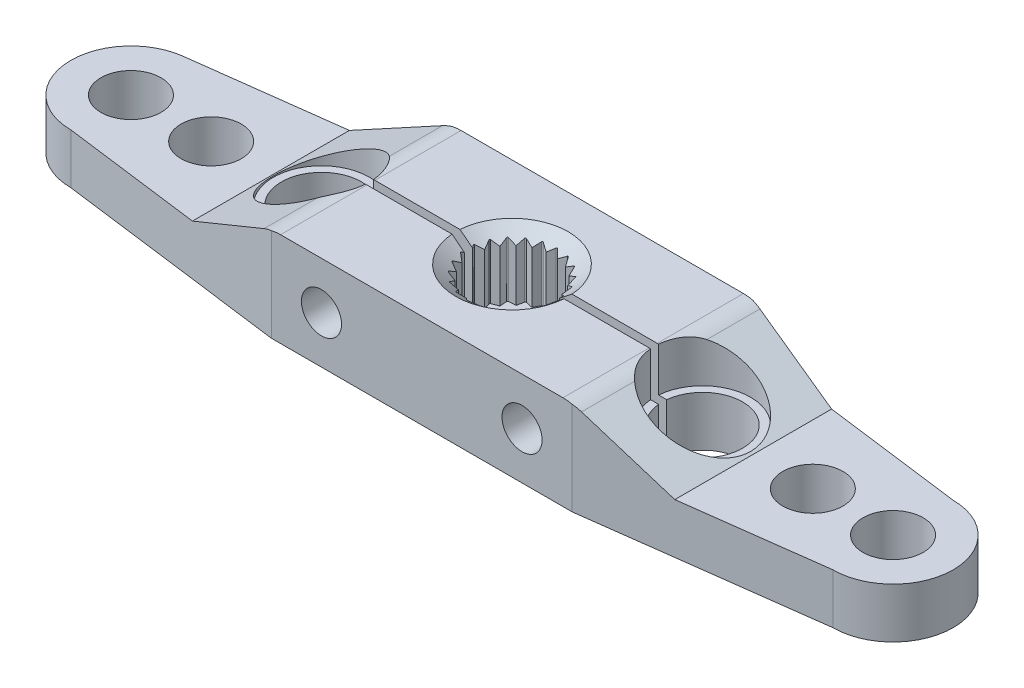
SolidWorks part; units mm, degrees
material "6061 Alloy"
ref_plane "Front Plane" through (0, 0, 0) normal (0, 0, 1) x (1, 0, 0)
ref_plane "Top Plane" through (0, 0, 0) normal (0, 1, 0) x (1, 0, 0)
ref_plane "Right Plane" through (0, 0, 0) normal (1, 0, 0) x (0, 0, -1)
sketch "Sketch1" plane through (0, 0, 0) normal (0, 1, 0) x (1, 0, 0)
  line L0 (-0.3401, -2.1423) -> (-0.1004, -1.9025) construction
  line L1 (-0.1004, -1.9025) -> (0.1972, -2.065) construction
  line L2 (0.2621, -2.046) -> (0.4246, -1.7484) construction
  line L3 (0.4246, -1.7484) -> (0.7558, -1.8205) construction
  line L4 (0.8127, -1.7839) -> (0.8848, -1.4526) construction
  line L5 (0.8848, -1.4526) -> (1.223, -1.4284) construction
  line L6 (1.2673, -1.3773) -> (1.2431, -1.0392) construction
  line L7 (1.2431, -1.0392) -> (1.5607, -0.9207) construction
  line L8 (1.5888, -0.8592) -> (1.4703, -0.5415) construction
  line L9 (1.4703, -0.5415) -> (1.7417, -0.3384) construction
  line L10 (1.7514, -0.2714) -> (1.5482, 0) construction
  line L11 (1.5482, 0) -> (1.7514, 0.2714) construction
  line L12 (1.7417, 0.3384) -> (1.4703, 0.5415) construction
  line L13 (1.4703, 0.5415) -> (1.5888, 0.8592) construction
  line L14 (1.5607, 0.9207) -> (1.2431, 1.0392) construction
  line L15 (1.2431, 1.0392) -> (1.2673, 1.3773) construction
  line L16 (1.223, 1.4284) -> (0.8848, 1.4526) construction
  line L17 (0.8848, 1.4526) -> (0.8127, 1.7839) construction
  line L18 (0.7558, 1.8205) -> (0.4246, 1.7484) construction
  line L19 (0.4246, 1.7484) -> (0.2621, 2.046) construction
  line L20 (0.1972, 2.065) -> (-0.1004, 1.9025) construction
  line L21 (-0.1004, 1.9025) -> (-0.3401, 2.1423) construction
  line L22 (-0.4077, 2.1423) -> (-0.6475, 1.9025) construction
  line L23 (-0.6475, 1.9025) -> (-0.945, 2.065) construction
  line L24 (-1.0099, 2.046) -> (-1.1724, 1.7484) construction
  line L25 (-1.1724, 1.7484) -> (-1.5037, 1.8205) construction
  line L26 (-1.5606, 1.7839) -> (-1.6326, 1.4526) construction
  line L27 (-1.6326, 1.4526) -> (-1.9708, 1.4284) construction
  line L28 (-2.0151, 1.3773) -> (-1.9909, 1.0392) construction
  line L29 (-1.9909, 1.0392) -> (-2.3085, 0.9207) construction
  line L30 (-2.3366, 0.8592) -> (-2.2182, 0.5415) construction
  line L31 (-2.2182, 0.5415) -> (-2.4896, 0.3384) construction
  line L32 (-2.4992, 0.2714) -> (-2.296, 0) construction
  line L33 (-2.296, 0) -> (-2.4992, -0.2714) construction
  line L34 (-2.4896, -0.3384) -> (-2.2182, -0.5415) construction
  line L35 (-2.2182, -0.5415) -> (-2.3366, -0.8592) construction
  line L36 (-2.3085, -0.9207) -> (-1.9909, -1.0392) construction
  line L37 (-1.9909, -1.0392) -> (-2.0151, -1.3773) construction
  line L38 (-1.9708, -1.4284) -> (-1.6326, -1.4526) construction
  line L39 (-1.6326, -1.4526) -> (-1.5606, -1.7839) construction
  line L40 (-1.5037, -1.8205) -> (-1.1724, -1.7484) construction
  line L41 (-1.1724, -1.7484) -> (-1.0099, -2.046) construction
  line L42 (-0.945, -2.065) -> (-0.6475, -1.9025) construction
  line L43 (-0.6475, -1.9025) -> (-0.4077, -2.1423) construction
  line L44 (-15.3739, 0) -> (14.6261, 0) construction
  line L46 (14.6261, 0) -> (18.6261, 0) construction
  line L47 (-0.3739, 0) -> (-0.3739, 4.5) construction
  line L48 (21.6261, 0) -> (21.6261, 4.5) construction
  line L49 (-7.8739, 4.5) -> (7.1261, 4.5)
  line L50 (18.6261, 0) -> (21.6261, 0) construction
  line L51 (7.1261, 4.5) -> (18.6261, 3)
  line L52 (7.1261, 4.5) -> (7.1261, -4.5) construction
  line L53 (7.1261, -4.5) -> (-7.8739, -4.5)
  line L54 (7.1261, -4.5) -> (18.6261, -3)
  line L55 (-7.8739, -4.5) -> (-19.3739, -3)
  line L56 (-7.8739, 4.5) -> (-7.8739, -4.5) construction
  line L57 (-19.3739, 0) -> (-22.3739, 0) construction
  line L59 (-15.3739, 0) -> (-19.3739, 0) construction
  line L61 (-7.8739, 4.5) -> (-19.7557, 2.9756)
  circle A0 centre (-0.3739, 0) radius 4.5 construction
  arc A1 (-0.4077, -2.1423) -> (-0.3401, -2.1423) centre (-0.3739, -2.1085) ccw construction
  arc A2 (0.1972, -2.065) -> (0.2621, -2.046) centre (0.2201, -2.023) ccw construction
  arc A3 (0.7558, -1.8205) -> (0.8127, -1.7839) centre (0.766, -1.7737) ccw construction
  arc A4 (1.223, -1.4284) -> (1.2673, -1.3773) centre (1.2195, -1.3807) ccw construction
  arc A5 (1.5607, -0.9207) -> (1.5888, -0.8592) centre (1.544, -0.8759) ccw construction
  arc A6 (1.7417, -0.3384) -> (1.7514, -0.2714) centre (1.7131, -0.3001) ccw construction
  arc A7 (1.7514, 0.2714) -> (1.7417, 0.3384) centre (1.7131, 0.3001) ccw construction
  arc A8 (1.5888, 0.8592) -> (1.5607, 0.9207) centre (1.544, 0.8759) ccw construction
  arc A9 (1.2673, 1.3773) -> (1.223, 1.4284) centre (1.2195, 1.3807) ccw construction
  arc A10 (0.8127, 1.7839) -> (0.7558, 1.8205) centre (0.766, 1.7737) ccw construction
  arc A11 (0.2621, 2.046) -> (0.1972, 2.065) centre (0.2201, 2.023) ccw construction
  arc A12 (-0.3401, 2.1423) -> (-0.4077, 2.1423) centre (-0.3739, 2.1085) ccw construction
  arc A13 (-0.945, 2.065) -> (-1.0099, 2.046) centre (-0.9679, 2.023) ccw construction
  arc A14 (-1.5037, 1.8205) -> (-1.5606, 1.7839) centre (-1.5138, 1.7737) ccw construction
  arc A15 (-1.9708, 1.4284) -> (-2.0151, 1.3773) centre (-1.9674, 1.3807) ccw construction
  arc A16 (-2.3085, 0.9207) -> (-2.3366, 0.8592) centre (-2.2918, 0.8759) ccw construction
  arc A17 (-2.4896, 0.3384) -> (-2.4992, 0.2714) centre (-2.4609, 0.3001) ccw construction
  arc A18 (-2.4992, -0.2714) -> (-2.4896, -0.3384) centre (-2.4609, -0.3001) ccw construction
  arc A19 (-2.3366, -0.8592) -> (-2.3085, -0.9207) centre (-2.2918, -0.8759) ccw construction
  arc A20 (-2.0151, -1.3773) -> (-1.9708, -1.4284) centre (-1.9674, -1.3807) ccw construction
  arc A21 (-1.5606, -1.7839) -> (-1.5037, -1.8205) centre (-1.5138, -1.7737) ccw construction
  arc A22 (-1.0099, -2.046) -> (-0.945, -2.065) centre (-0.9679, -2.023) ccw construction
  circle A23 centre (18.6261, 0) radius 1.5
  circle A24 centre (14.6261, 0) radius 1.5
  arc A25 (18.6261, -3) -> (18.6261, 3) centre (18.6261, 0) ccw
  circle A26 centre (9.1261, 0) radius 2
  circle A27 centre (-9.8739, 0) radius 2
  arc A28 (-19.3739, -3) -> (-19.7557, 2.9756) centre (-19.3739, 0) cw
  circle A29 centre (-15.3739, 0) radius 1.5
  circle A30 centre (-19.3739, 0) radius 1.5
  circle A31 centre (-0.3739, 0) radius 1.5
  circle A32 centre (-0.3739, 0) radius 2.1425 construction
  point P109 (-0.3739, -4.5)
  dimension "D2" = 3
  dimension "D3" = 3
  dimension "D4" = 4
  dimension "D5" = 4
  dimension "D6" = 3
  dimension "D7" = 3
  dimension "D8" = 3
  dimension "D9" = 3
  dimension "D12" = 30
  dimension "D1" = 22
  dimension "D10" = 44
  dimension "D11" = 15
extrude "Boss-Extrude1" add sketch "Sketch1" along normal blind 2.5
sketch "Sketch3" plane through (0, 2.5, 0) normal (0, 1, 0) x (1, 0, 0)
  line L0 (-0.3386, -2.2396) -> (-0.0879, -1.989)
  line L1 (-0.0879, -1.989) -> (0.2231, -2.1589)
  line L2 (0.291, -2.139) -> (0.4609, -1.8279)
  line L3 (0.4609, -1.8279) -> (0.8072, -1.9032)
  line L4 (0.8667, -1.865) -> (0.942, -1.5187)
  line L5 (0.942, -1.5187) -> (1.2955, -1.4934)
  line L6 (1.3419, -1.4399) -> (1.3166, -1.0864)
  line L7 (1.3166, -1.0864) -> (1.6487, -0.9625)
  line L8 (1.678, -0.8982) -> (1.5542, -0.5661)
  line L9 (1.5542, -0.5661) -> (1.8379, -0.3537)
  line L10 (1.848, -0.2837) -> (1.6356, 0)
  line L11 (1.6356, 0) -> (1.848, 0.2837)
  line L12 (1.8379, 0.3537) -> (1.5542, 0.5661)
  line L13 (1.5542, 0.5661) -> (1.678, 0.8982)
  line L14 (1.6487, 0.9625) -> (1.3166, 1.0864)
  line L15 (1.3166, 1.0864) -> (1.3419, 1.4399)
  line L16 (1.2955, 1.4934) -> (0.942, 1.5187)
  line L17 (0.942, 1.5187) -> (0.8667, 1.865)
  line L18 (0.8072, 1.9032) -> (0.4609, 1.8279)
  line L19 (0.4609, 1.8279) -> (0.291, 2.139)
  line L20 (0.2231, 2.1589) -> (-0.0879, 1.989)
  line L21 (-0.0879, 1.989) -> (-0.3386, 2.2396)
  line L22 (-0.4093, 2.2396) -> (-0.6599, 1.989)
  line L23 (-0.6599, 1.989) -> (-0.971, 2.1589)
  line L24 (-1.0388, 2.139) -> (-1.2087, 1.8279)
  line L25 (-1.2087, 1.8279) -> (-1.555, 1.9032)
  line L26 (-1.6145, 1.865) -> (-1.6898, 1.5187)
  line L27 (-1.6898, 1.5187) -> (-2.0434, 1.4934)
  line L28 (-2.0897, 1.4399) -> (-2.0644, 1.0864)
  line L29 (-2.0644, 1.0864) -> (-2.3965, 0.9625)
  line L30 (-2.4259, 0.8982) -> (-2.302, 0.5661)
  line L31 (-2.302, 0.5661) -> (-2.5857, 0.3537)
  line L32 (-2.5958, 0.2837) -> (-2.3834, 0)
  line L33 (-2.3834, 0) -> (-2.5958, -0.2837)
  line L34 (-2.5857, -0.3537) -> (-2.302, -0.5661)
  line L35 (-2.302, -0.5661) -> (-2.4259, -0.8982)
  line L36 (-2.3965, -0.9625) -> (-2.0644, -1.0864)
  line L37 (-2.0644, -1.0864) -> (-2.0897, -1.4399)
  line L38 (-2.0434, -1.4934) -> (-1.6898, -1.5187)
  line L39 (-1.6898, -1.5187) -> (-1.6145, -1.865)
  line L40 (-1.555, -1.9032) -> (-1.2087, -1.8279)
  line L41 (-1.2087, -1.8279) -> (-1.0388, -2.139)
  line L42 (-0.971, -2.1589) -> (-0.6599, -1.989)
  line L43 (-0.6599, -1.989) -> (-0.4093, -2.2396)
  line L44 (-7.8739, -4.5) -> (-7.8739, 4.5)
  line L45 (-7.8739, 4.5) -> (7.1261, 4.5)
  line L46 (7.1261, 4.5) -> (7.1261, -4.5)
  line L47 (7.1261, -4.5) -> (-7.8739, -4.5)
  circle A0 centre (-0.3739, 0) radius 2.2399 construction
  arc A1 (-0.4093, -2.2396) -> (-0.3386, -2.2396) centre (-0.3739, -2.2043) ccw
  arc A2 (0.2231, -2.1589) -> (0.291, -2.139) centre (0.2471, -2.115) ccw
  arc A3 (0.8072, -1.9032) -> (0.8667, -1.865) centre (0.8178, -1.8544) ccw
  arc A4 (1.2955, -1.4934) -> (1.3419, -1.4399) centre (1.292, -1.4435) ccw
  arc A5 (1.6487, -0.9625) -> (1.678, -0.8982) centre (1.6312, -0.9157) ccw
  arc A6 (1.8379, -0.3537) -> (1.848, -0.2837) centre (1.8079, -0.3137) ccw
  arc A7 (1.848, 0.2837) -> (1.8379, 0.3537) centre (1.8079, 0.3137) ccw
  arc A8 (1.678, 0.8982) -> (1.6487, 0.9625) centre (1.6312, 0.9157) ccw
  arc A9 (1.3419, 1.4399) -> (1.2955, 1.4934) centre (1.292, 1.4435) ccw
  arc A10 (0.8667, 1.865) -> (0.8072, 1.9032) centre (0.8178, 1.8544) ccw
  arc A11 (0.291, 2.139) -> (0.2231, 2.1589) centre (0.2471, 2.115) ccw
  arc A12 (-0.3386, 2.2396) -> (-0.4093, 2.2396) centre (-0.3739, 2.2043) ccw
  arc A13 (-0.971, 2.1589) -> (-1.0388, 2.139) centre (-0.9949, 2.115) ccw
  arc A14 (-1.555, 1.9032) -> (-1.6145, 1.865) centre (-1.5656, 1.8544) ccw
  arc A15 (-2.0434, 1.4934) -> (-2.0897, 1.4399) centre (-2.0398, 1.4435) ccw
  arc A16 (-2.3965, 0.9625) -> (-2.4259, 0.8982) centre (-2.379, 0.9157) ccw
  arc A17 (-2.5857, 0.3537) -> (-2.5958, 0.2837) centre (-2.5558, 0.3137) ccw
  arc A18 (-2.5958, -0.2837) -> (-2.5857, -0.3537) centre (-2.5558, -0.3137) ccw
  arc A19 (-2.4259, -0.8982) -> (-2.3965, -0.9625) centre (-2.379, -0.9157) ccw
  arc A20 (-2.0897, -1.4399) -> (-2.0434, -1.4934) centre (-2.0398, -1.4435) ccw
  arc A21 (-1.6145, -1.865) -> (-1.555, -1.9032) centre (-1.5656, -1.8544) ccw
  arc A22 (-1.0388, -2.139) -> (-0.971, -2.1589) centre (-0.9949, -2.115) ccw
extrude "Boss-Extrude2" add sketch "Sketch3" along normal blind 2.2
ref_plane "Plane1" through (-7.8739, 2.5, 0) normal (0, 0, 1) x (1, 0, 0)
ref_plane "Plane2" through (-7.8739, 4.7, -4.5) normal (0, 0, 1) x (1, 0, 0)
sketch "Sketch7" plane through (-0.7089, 0, 5.4346) normal (-0.1293, 0, 0.9916) x (0.9916, 0, 0.1293)
  line L0 (-7.2257, 2.5) -> (-7.2257, 4.7)
  line L1 (-7.2257, 4.7) -> (-11.791, 2.5)
  line L2 (-18.8232, 2.5) -> (-7.2257, 2.5) construction
  line L3 (-11.791, 2.5) -> (-7.2257, 2.5)
extrude "Boss-Extrude3" add sketch "Sketch7" along direction (0, 0, 1) on the side against the normal up to surface (9 mm away) up to face at (-13.8148, 1.25, -3.7378)
sketch "Sketch8" plane through (0, 2.5, 0) normal (0, -1, 0) x (1, 0, 0)
  circle A0 centre (-9.8739, 0) radius 2.4
  circle A1 centre (-9.8739, 0) radius 2
  circle A2 centre (-9.8739, 0) radius 2
  dimension "D1" = 0
extrude "Cut-Extrude1" cut sketch "Sketch8" against normal through all contours A0
sketch "Sketch9" plane through (0.6963, 0, -5.3387) normal (0.1293, 0, -0.9916) x (-0.9916, 0, -0.1293)
  line L0 (-6.4842, 2.5) -> (-6.4842, 4.7)
  line L1 (-6.4842, 4.7) -> (-11.0494, 2.5)
  line L2 (-18.0816, 2.5) -> (-6.4842, 2.5) construction
  line L3 (-11.0494, 2.5) -> (-6.4842, 2.5)
extrude "Boss-Extrude4" add sketch "Sketch9" along direction (0, 0, -1) on the side against the normal up to surface (9 mm away) up to face at (12.8761, 1.25, 3.75)
sketch "Sketch10" plane through (0, 2.5, 0) normal (0, -1, 0) x (1, 0, 0)
  circle A0 centre (9.1261, 0) radius 2.4
  circle A1 centre (9.1261, 0) radius 2
  circle A2 centre (9.1261, 0) radius 2
  dimension "D1" = 0
extrude "Cut-Extrude2" cut sketch "Sketch10" against normal blind 2.5 contours A0
sketch "Sketch18" plane through (0, 2.5, 0) normal (0, 1, 0) x (1, 0, 0)
  line L44 (-0.3386, -2.2396) -> (-0.0879, -1.989)
  line L45 (-0.0879, -1.989) -> (0.2231, -2.1589)
  line L46 (0.291, -2.139) -> (0.4609, -1.8279)
  line L47 (0.4609, -1.8279) -> (0.8072, -1.9032)
  line L48 (0.8667, -1.865) -> (0.942, -1.5187)
  line L49 (0.942, -1.5187) -> (1.2955, -1.4934)
  line L50 (1.3419, -1.4399) -> (1.3166, -1.0864)
  line L51 (1.3166, -1.0864) -> (1.6487, -0.9625)
  line L52 (1.678, -0.8982) -> (1.5542, -0.5661)
  line L53 (1.5542, -0.5661) -> (1.8379, -0.3537)
  line L54 (1.848, -0.2837) -> (1.6356, 0)
  line L55 (1.6356, 0) -> (1.848, 0.2837)
  line L56 (1.8379, 0.3537) -> (1.5542, 0.5661)
  line L57 (1.5542, 0.5661) -> (1.678, 0.8982)
  line L58 (1.6487, 0.9625) -> (1.3166, 1.0864)
  line L59 (1.3166, 1.0864) -> (1.3419, 1.4399)
  line L60 (1.2955, 1.4934) -> (0.942, 1.5187)
  line L61 (0.942, 1.5187) -> (0.8667, 1.865)
  line L62 (0.8072, 1.9032) -> (0.4609, 1.8279)
  line L63 (0.4609, 1.8279) -> (0.291, 2.139)
  line L64 (0.2231, 2.1589) -> (-0.0879, 1.989)
  line L65 (-0.0879, 1.989) -> (-0.3386, 2.2396)
  line L66 (-0.4093, 2.2396) -> (-0.6599, 1.989)
  line L67 (-0.6599, 1.989) -> (-0.971, 2.1589)
  line L68 (-1.0388, 2.139) -> (-1.2087, 1.8279)
  line L69 (-1.2087, 1.8279) -> (-1.555, 1.9032)
  line L70 (-1.6145, 1.865) -> (-1.6898, 1.5187)
  line L71 (-1.6898, 1.5187) -> (-2.0434, 1.4934)
  line L72 (-2.0897, 1.4399) -> (-2.0644, 1.0864)
  line L73 (-2.0644, 1.0864) -> (-2.3965, 0.9625)
  line L74 (-2.4259, 0.8982) -> (-2.302, 0.5661)
  line L75 (-2.302, 0.5661) -> (-2.5857, 0.3537)
  line L76 (-2.5958, 0.2837) -> (-2.3834, 0)
  line L77 (-2.3834, 0) -> (-2.5958, -0.2837)
  line L78 (-2.5857, -0.3537) -> (-2.302, -0.5661)
  line L79 (-2.302, -0.5661) -> (-2.4259, -0.8982)
  line L80 (-2.3965, -0.9625) -> (-2.0644, -1.0864)
  line L81 (-2.0644, -1.0864) -> (-2.0897, -1.4399)
  line L82 (-2.0434, -1.4934) -> (-1.6898, -1.5187)
  line L83 (-1.6898, -1.5187) -> (-1.6145, -1.865)
  line L84 (-1.555, -1.9032) -> (-1.2087, -1.8279)
  line L85 (-1.2087, -1.8279) -> (-1.0388, -2.139)
  line L86 (-0.971, -2.1589) -> (-0.6599, -1.989)
  line L87 (-0.6599, -1.989) -> (-0.4093, -2.2396)
  line L88 (-0.3386, -2.2396) -> (-0.0879, -1.989)
  line L89 (-0.0879, -1.989) -> (0.2231, -2.1589)
  line L90 (0.291, -2.139) -> (0.4609, -1.8279)
  line L91 (0.4609, -1.8279) -> (0.8072, -1.9032)
  line L92 (0.8667, -1.865) -> (0.942, -1.5187)
  line L93 (0.942, -1.5187) -> (1.2955, -1.4934)
  line L94 (1.3419, -1.4399) -> (1.3166, -1.0864)
  line L95 (1.3166, -1.0864) -> (1.6487, -0.9625)
  line L96 (1.678, -0.8982) -> (1.5542, -0.5661)
  line L97 (1.5542, -0.5661) -> (1.8379, -0.3537)
  line L98 (1.848, -0.2837) -> (1.6356, 0)
  line L99 (1.6356, 0) -> (1.848, 0.2837)
  line L100 (1.8379, 0.3537) -> (1.5542, 0.5661)
  line L101 (1.5542, 0.5661) -> (1.678, 0.8982)
  line L102 (1.6487, 0.9625) -> (1.3166, 1.0864)
  line L103 (1.3166, 1.0864) -> (1.3419, 1.4399)
  line L104 (1.2955, 1.4934) -> (0.942, 1.5187)
  line L105 (0.942, 1.5187) -> (0.8667, 1.865)
  line L106 (0.8072, 1.9032) -> (0.4609, 1.8279)
  line L107 (0.4609, 1.8279) -> (0.291, 2.139)
  line L108 (0.2231, 2.1589) -> (-0.0879, 1.989)
  line L109 (-0.0879, 1.989) -> (-0.3386, 2.2396)
  line L110 (-0.4093, 2.2396) -> (-0.6599, 1.989)
  line L111 (-0.6599, 1.989) -> (-0.971, 2.1589)
  line L112 (-1.0388, 2.139) -> (-1.2087, 1.8279)
  line L113 (-1.2087, 1.8279) -> (-1.555, 1.9032)
  line L114 (-1.6145, 1.865) -> (-1.6898, 1.5187)
  line L115 (-1.6898, 1.5187) -> (-2.0434, 1.4934)
  line L116 (-2.0897, 1.4399) -> (-2.0644, 1.0864)
  line L117 (-2.0644, 1.0864) -> (-2.3965, 0.9625)
  line L118 (-2.4259, 0.8982) -> (-2.302, 0.5661)
  line L119 (-2.302, 0.5661) -> (-2.5857, 0.3537)
  line L120 (-2.5958, 0.2837) -> (-2.3834, 0)
  line L121 (-2.3834, 0) -> (-2.5958, -0.2837)
  line L122 (-2.5857, -0.3537) -> (-2.302, -0.5661)
  line L123 (-2.302, -0.5661) -> (-2.4259, -0.8982)
  line L124 (-2.3965, -0.9625) -> (-2.0644, -1.0864)
  line L125 (-2.0644, -1.0864) -> (-2.0897, -1.4399)
  line L126 (-2.0434, -1.4934) -> (-1.6898, -1.5187)
  line L127 (-1.6898, -1.5187) -> (-1.6145, -1.865)
  line L128 (-1.555, -1.9032) -> (-1.2087, -1.8279)
  line L129 (-1.2087, -1.8279) -> (-1.0388, -2.139)
  line L130 (-0.971, -2.1589) -> (-0.6599, -1.989)
  line L131 (-0.6599, -1.989) -> (-0.4093, -2.2396)
  circle A0 centre (-0.3739, 0) radius 1.5 construction
  circle A1 centre (-0.3739, 0) radius 1.5
  arc A22 (-0.4093, -2.2396) -> (-0.3386, -2.2396) centre (-0.3739, -2.2043) ccw
  arc A23 (0.2231, -2.1589) -> (0.291, -2.139) centre (0.2471, -2.115) ccw
  arc A24 (0.8072, -1.9032) -> (0.8667, -1.865) centre (0.8178, -1.8544) ccw
  arc A25 (1.2955, -1.4934) -> (1.3419, -1.4399) centre (1.292, -1.4435) ccw
  arc A26 (1.6487, -0.9625) -> (1.678, -0.8982) centre (1.6312, -0.9157) ccw
  arc A27 (1.8379, -0.3537) -> (1.848, -0.2837) centre (1.8079, -0.3137) ccw
  arc A28 (1.848, 0.2837) -> (1.8379, 0.3537) centre (1.8079, 0.3137) ccw
  arc A29 (1.678, 0.8982) -> (1.6487, 0.9625) centre (1.6312, 0.9157) ccw
  arc A30 (1.3419, 1.4399) -> (1.2955, 1.4934) centre (1.292, 1.4435) ccw
  arc A31 (0.8667, 1.865) -> (0.8072, 1.9032) centre (0.8178, 1.8544) ccw
  arc A32 (0.291, 2.139) -> (0.2231, 2.1589) centre (0.2471, 2.115) ccw
  arc A33 (-0.3386, 2.2396) -> (-0.4093, 2.2396) centre (-0.3739, 2.2043) ccw
  arc A34 (-0.971, 2.1589) -> (-1.0388, 2.139) centre (-0.9949, 2.115) ccw
  arc A35 (-1.555, 1.9032) -> (-1.6145, 1.865) centre (-1.5656, 1.8544) ccw
  arc A36 (-2.0434, 1.4934) -> (-2.0897, 1.4399) centre (-2.0398, 1.4435) ccw
  arc A37 (-2.3965, 0.9625) -> (-2.4259, 0.8982) centre (-2.379, 0.9157) ccw
  arc A38 (-2.5857, 0.3537) -> (-2.5958, 0.2837) centre (-2.5558, 0.3137) ccw
  arc A39 (-2.5958, -0.2837) -> (-2.5857, -0.3537) centre (-2.5558, -0.3137) ccw
  arc A40 (-2.4259, -0.8982) -> (-2.3965, -0.9625) centre (-2.379, -0.9157) ccw
  arc A41 (-2.0897, -1.4399) -> (-2.0434, -1.4934) centre (-2.0398, -1.4435) ccw
  arc A42 (-1.6145, -1.865) -> (-1.555, -1.9032) centre (-1.5656, -1.8544) ccw
  arc A43 (-1.0388, -2.139) -> (-0.971, -2.1589) centre (-0.9949, -2.115) ccw
  arc A44 (-0.4093, -2.2396) -> (-0.3386, -2.2396) centre (-0.3739, -2.2043) ccw
  arc A45 (0.2231, -2.1589) -> (0.291, -2.139) centre (0.2471, -2.115) ccw
  arc A46 (0.8072, -1.9032) -> (0.8667, -1.865) centre (0.8178, -1.8544) ccw
  arc A47 (1.2955, -1.4934) -> (1.3419, -1.4399) centre (1.292, -1.4435) ccw
  arc A48 (1.6487, -0.9625) -> (1.678, -0.8982) centre (1.6312, -0.9157) ccw
  arc A49 (1.8379, -0.3537) -> (1.848, -0.2837) centre (1.8079, -0.3137) ccw
  arc A50 (1.848, 0.2837) -> (1.8379, 0.3537) centre (1.8079, 0.3137) ccw
  arc A51 (1.678, 0.8982) -> (1.6487, 0.9625) centre (1.6312, 0.9157) ccw
  arc A52 (1.3419, 1.4399) -> (1.2955, 1.4934) centre (1.292, 1.4435) ccw
  arc A53 (0.8667, 1.865) -> (0.8072, 1.9032) centre (0.8178, 1.8544) ccw
  arc A54 (0.291, 2.139) -> (0.2231, 2.1589) centre (0.2471, 2.115) ccw
  arc A55 (-0.3386, 2.2396) -> (-0.4093, 2.2396) centre (-0.3739, 2.2043) ccw
  arc A56 (-0.971, 2.1589) -> (-1.0388, 2.139) centre (-0.9949, 2.115) ccw
  arc A57 (-1.555, 1.9032) -> (-1.6145, 1.865) centre (-1.5656, 1.8544) ccw
  arc A58 (-2.0434, 1.4934) -> (-2.0897, 1.4399) centre (-2.0398, 1.4435) ccw
  arc A59 (-2.3965, 0.9625) -> (-2.4259, 0.8982) centre (-2.379, 0.9157) ccw
  arc A60 (-2.5857, 0.3537) -> (-2.5958, 0.2837) centre (-2.5558, 0.3137) ccw
  arc A61 (-2.5958, -0.2837) -> (-2.5857, -0.3537) centre (-2.5558, -0.3137) ccw
  arc A62 (-2.4259, -0.8982) -> (-2.3965, -0.9625) centre (-2.379, -0.9157) ccw
  arc A63 (-2.0897, -1.4399) -> (-2.0434, -1.4934) centre (-2.0398, -1.4435) ccw
  arc A64 (-1.6145, -1.865) -> (-1.555, -1.9032) centre (-1.5656, -1.8544) ccw
  arc A65 (-1.0388, -2.139) -> (-0.971, -2.1589) centre (-0.9949, -2.115) ccw
  dimension "D1" = 0
extrude "Cut-Extrude5" cut sketch "Sketch18" against normal blind 1
sketch "Sketch13" plane through (0, 0, 0) normal (0, 0, 1) x (1, 0, 0)
  line L0 (-0.3739, 2.5) -> (-0.3739, 4.7)
  line L1 (-0.3739, 4.7) -> (-3.1739, 4.7)
  line L2 (7.1261, 4.7) -> (-7.8739, 4.7) construction
  line L3 (-3.1739, 4.7) -> (-0.3739, 2.5)
  line L6 (1.1261, 2.5) -> (-1.8739, 2.5) construction
revolve "Cut-Revolve1" cut sketch "Sketch13" angle 360 about L0
fillet "Fillet2" radius 2 2 edges at (7.1261, 4.7, 2.9133) (-7.8739, 4.7, 2.9133)
sketch "Sketch14" plane through (0, 4.7, 0) normal (0, 1, 0) x (1, 0, 0)
  line L0 (0, 0) -> (-10, 0)
  line L1 (-62.8739, 0) -> (47.1261, 0) construction
  line L2 (0, 0.2) -> (-10, 0.2)
  line L3 (0, -0.2) -> (-10, -0.2)
  line L4 (0, 0) -> (0, 1.5) construction
  line L5 (-10, 0.2) -> (-10, -0.2)
  line L6 (0, -0.2) -> (10, -0.2)
  line L7 (10, 0.2) -> (10, -0.2)
  line L8 (0, 0.2) -> (10, 0.2)
  dimension "D1" = 0.2
  dimension "D2" = 0.2
extrude "Cut-Extrude3" cut sketch "Sketch14" against normal through all contours L3 L5 L2 L8 L7 L6
sketch "Sketch15" plane through (0, 0, 4.5) normal (0, 0, 1) x (1, 0, 0)
  line L0 (-0.3739, 4.7) -> (-0.3739, 0) construction
  line L1 (-7.4137, 4.7) -> (6.6658, 4.7) construction
  line L2 (-7.8739, 0) -> (7.1261, 0) construction
  line L3 (-5.3739, 4.7) -> (-5.3739, 0) construction
  line L4 (4.6261, 4.7) -> (4.6261, 0) construction
  line L5 (-5.3739, 2.35) -> (4.6261, 2.35) construction
  circle A0 centre (-5.3739, 2.35) radius 1
  circle A1 centre (4.6261, 2.35) radius 1
  dimension "D1" = 5
  dimension "D2" = 5
extrude "Cut-Extrude4" cut sketch "Sketch15" against normal through all
